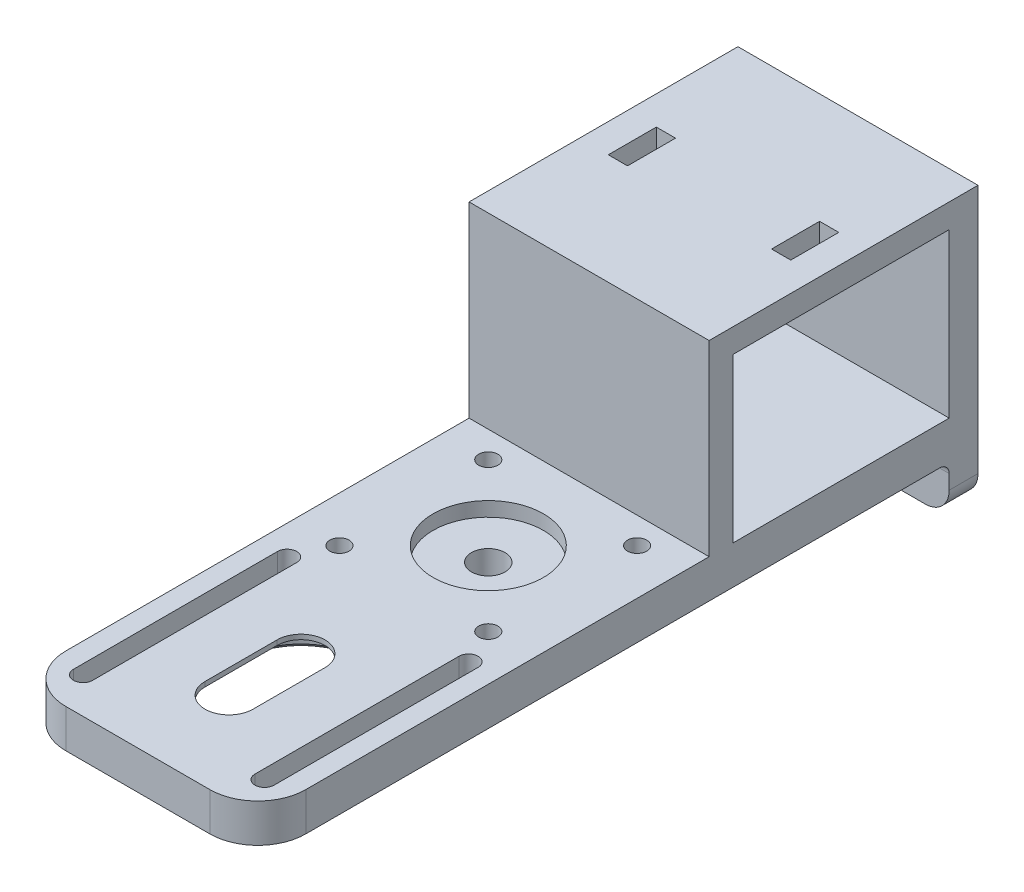
SolidWorks part; units mm, degrees
ref_plane "Front Plane" through (0, 0, 0) normal (1, 0, 0) x (0, 1, 0)
ref_plane "Top Plane" through (0, 0, 0) normal (0, 0, 1) x (0, 1, 0)
ref_plane "Right Plane" through (0, 0, 0) normal (0, 1, 0) x (-1, 0, 0)
sketch "Sketch1" plane through (0, 0, 0) normal (0, 0, 1) x (0, 1, 0)
  line L0 (1.5, 25) -> (1.5, -15) construction
  line L1 (-2.5, 25) -> (7.5, 25)
  line L2 (-2.5, 25) -> (-2.5, -25)
  line L3 (-2.5, -25) -> (7.5, -25)
  line L4 (7.5, 25) -> (7.5, -25)
  line L5 (-2.5, 0) -> (7.5, 0) construction
  circle A0 centre (1.5, -15) radius 2
  circle A1 centre (1.5, 15) radius 2
  point P0 (0, 0)
  dimension "D3" = 4
  dimension "D1" = 50
  dimension "D2" = 10
  dimension "D4" = 30
  dimension "D5" = 4
extrude "Boss-Extrude1" add sketch "Sketch1" along normal blind 6
sketch "Sketch2" plane through (0, 7.5, 0) normal (0, 1, 0) x (-1, 0, 0)
  line L0 (25, 6) -> (25, 0) construction
  line L1 (-25, 0) -> (25, 0)
  line L2 (-25, 0) -> (-25, 150)
  line L3 (-25, 150) -> (25, 150)
  line L4 (25, 0) -> (25, 150)
  dimension "D1" = 150
extrude "Boss-Extrude2" add sketch "Sketch2" along normal blind 8
fillet "Fillet1" radius 2 1 edges at (0, 7.5, 6)
sketch "Sketch3" plane through (25, 0, 0) normal (1, 0, 0) x (0, 1, 0)
  line L1 (15.5, 0) -> (54.5, 0)
  line L2 (15.5, 0) -> (15.5, 6)
  line L3 (15.5, 6) -> (54.5, 6)
  line L4 (54.5, 0) -> (54.5, 6)
  line L6 (-2.5, 6) -> (5.5, 6) construction
  dimension "D1" = 39
extrude "Boss-Extrude3" add sketch "Sketch3" against normal up to surface (50 mm away) up to face at (-25, 6.702, 45.6551)
sketch "Sketch16" plane through (25, 0, 0) normal (1, 0, 0) x (0, 1, 0)
  line L0 (54.5, 6) -> (54.5, 56)
  line L1 (54.5, 56) -> (15.5, 56)
  line L2 (15.5, 150) -> (15.5, 6) construction
  line L3 (15.5, 56) -> (15.5, 51)
  line L4 (15.5, 51) -> (49.5, 51)
  line L5 (49.5, 51) -> (49.5, 6)
  line L6 (54.5, 6) -> (15.5, 6) construction
  line L7 (49.5, 6) -> (54.5, 6)
  dimension "D1" = 5
  dimension "D2" = 50
extrude "Boss-Extrude4" add sketch "Sketch16" against normal up to surface (50 mm away) up to face at (-25, 17.3238, 36.8429)
sketch "Sketch11" plane through (0, 7.5, 0) normal (0, -1, 0) x (1, 0, 0)
  line L1 (0, 77) -> (11.9823, 77) construction
  line L2 (0, 77) -> (0, 33.0744) construction
  line L3 (-25, 56) -> (25, 56) construction
  circle A0 centre (-15.5, 92.5) radius 2
  circle A1 centre (15.5, 92.5) radius 2
  circle A2 centre (15.5, 61.5) radius 2
  circle A3 centre (-15.5, 61.5) radius 2
  circle A4 centre (0, 77) radius 3.5
  point P0 (0, 77)
  dimension "D4" = 4
  dimension "D5" = 7
  dimension "D1" = 21
  dimension "D2" = 15.5
  dimension "D3" = 15.5
extrude "Cut-Extrude7" cut sketch "Sketch11" against normal through all
sketch "Sketch6" plane through (0, 7.5, 0) normal (0, -1, 0) x (1, 0, 0)
  line L0 (0, 150) -> (0, 143.4) construction
  line L1 (-25, 150) -> (25, 150) construction
  line L2 (-25, 6) -> (25, 6) construction
  line L3 (-12.4, 131) -> (-12.4, 116)
  line L4 (12.4, 131) -> (12.4, 116)
  line L5 (0, 61.8) -> (0, 0) construction
  arc A0 (12.4, 131) -> (-12.4, 131) centre (0, 131) ccw
  arc A1 (-12.4, 116) -> (12.4, 116) centre (0, 116) ccw
  dimension "D1" = 24.8
  dimension "D2" = 125
  dimension "D3" = 15
extrude "Cut-Extrude2" cut sketch "Sketch6" against normal offset from surface (7 mm away) 1 up to face at (-13.5, 15.5, 61.5)
chamfer "Chamfer1" distance 1 angle 45 4 edges at (0, 7.5, 143.4) (0, 7.5, 103.6) (12.4, 7.5, 123.5) (-12.4, 7.5, 123.5)
sketch "Sketch8" plane through (0, 14.5, 0) normal (0, -1, 0) x (1, 0, 0)
  line L0 (-5, 131) -> (-5, 116)
  line L1 (5, 116) -> (5, 131)
  arc A0 (5, 131) -> (-5, 131) centre (0, 131) ccw
  circle A1 centre (0, 131) radius 12.4 construction
  circle A2 centre (0, 131) radius 12.4 construction
  arc A3 (-5, 116) -> (5, 116) centre (0, 116) ccw
  dimension "D1" = 10
extrude "Cut-Extrude4" cut sketch "Sketch8" against normal up to next
fillet "Fillet2" radius 10 2 edges at (-25, 11.5, 150) (25, 11.5, 150)
fillet "Fillet3" radius 5 2 edges at (-25, -2.5, 3) (25, -2.5, 3)
sketch "Sketch10" plane through (0, 7.5, 0) normal (0, -1, 0) x (1, 0, 0)
  line L0 (-13.4, 123.5) -> (12.4, 123.5) construction
  line L1 (-13.4, 116) -> (-13.4, 131) construction
  line L2 (12.4, 131) -> (12.4, 116) construction
  line L3 (-18.9, 100) -> (-18.9, 142.5) construction
  line L4 (-20.9, 100) -> (-20.9, 142.5)
  line L5 (-16.9, 100) -> (-16.9, 142.5)
  line L7 (-15, 150) -> (15, 150) construction
  line L10 (0, 142.4) -> (0, 103.6) construction
  line L11 (18.9, 100) -> (18.9, 142.5) construction
  line L14 (20.9, 100) -> (20.9, 142.5)
  line L17 (16.9, 100) -> (16.9, 142.5)
  arc A0 (13.4, 131) -> (-13.4, 131) centre (0, 131) ccw construction
  arc A1 (13.4, 131) -> (-13.4, 131) centre (0, 131) ccw construction
  arc A2 (-20.9, 100) -> (-16.9, 100) centre (-18.9, 100) ccw
  arc A3 (-16.9, 142.5) -> (-20.9, 142.5) centre (-18.9, 142.5) ccw
  arc A8 (-12.4, 116) -> (12.4, 116) centre (0, 116) ccw construction
  arc A15 (20.9, 100) -> (16.9, 100) centre (18.9, 100) cw
  arc A16 (16.9, 142.5) -> (20.9, 142.5) centre (18.9, 142.5) cw
  point P11 (-18.9, 121.25)
  point P20 (-18.9, 157.6)
  point P21 (18.9, 121.25)
  point P35 (18.9, 87.4)
  point P42 (18.9, 157.6)
  dimension "D1" = 2
  dimension "D2" = 7.5
  dimension "D3" = 5.5
  dimension "D4" = 42.5
extrude "Cut-Extrude6" cut sketch "Sketch10" against normal through all
sketch "Sketch14" plane through (0, 15.5, 0) normal (0, 1, 0) x (-1, 0, 0)
  circle A0 centre (0, 77) radius 11.5
  dimension "D1" = 23
extrude "Cut-Extrude9" cut sketch "Sketch14" against normal blind 3
sketch "Sketch17" plane through (0, 54.5, 0) normal (0, 1, 0) x (-1, 0, 0)
  line L0 (0, 56) -> (0, 0) construction
  line L1 (25, 56) -> (-25, 56) construction
  line L2 (25, 0) -> (-25, 0) construction
  line L3 (19, 23) -> (15, 23)
  line L4 (-19, 33) -> (-15, 33)
  line L5 (-19, 33) -> (-19, 23)
  line L6 (-19, 23) -> (-15, 23)
  line L7 (-15, 33) -> (-15, 23)
  line L8 (15, 33) -> (15, 23)
  line L9 (19, 33) -> (15, 33)
  line L10 (19, 33) -> (19, 23)
  line L11 (25, 28) -> (-25, 28) construction
  line L12 (25, 56) -> (25, 0) construction
  line L13 (-25, 0) -> (-25, 56) construction
  point P20 (-19, 28)
  dimension "D1" = 4
  dimension "D2" = 10
  dimension "D3" = 15
extrude "Cut-Extrude10" cut sketch "Sketch17" against normal up to next
